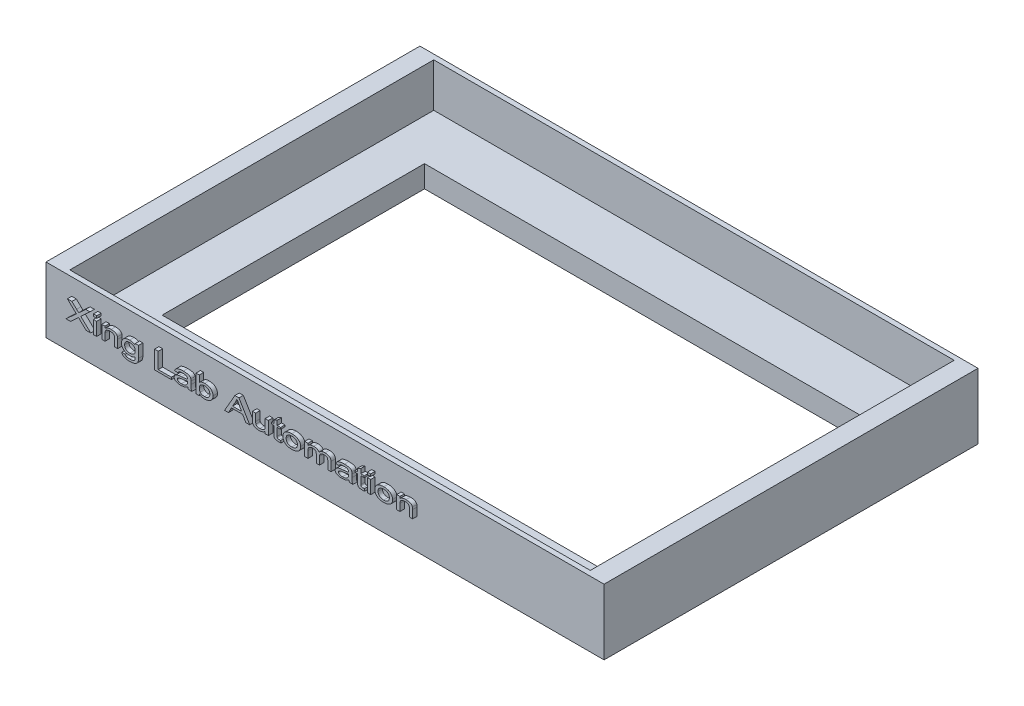
SolidWorks part; units mm, degrees
ref_plane "前视基准面" through (0, 0, 0) normal (0, 0, 1) x (1, 0, 0)
ref_plane "上视基准面" through (0, 0, 0) normal (0, 1, 0) x (1, 0, 0)
ref_plane "右视基准面" through (0, 0, 0) normal (1, 0, 0) x (0, 0, -1)
other "Configuration Table"
sketch "草图1" plane through (0, 0, 0) normal (0, 1, 0) x (1, 0, 0)
  line L0 (-59.5, 42.75) -> (-59.5, -42.7501)
  line L1 (-63.8, -42.75) -> (63.8, -42.75)
  line L3 (-63.8, 42.75) -> (63.8, 42.75)
  line L4 (63.8, -42.75) -> (63.8, 42.75)
  line L5 (-63.8, -42.75) -> (63.8, 42.75) construction
  line L6 (-63.8, 42.75) -> (63.8, -42.75) construction
  line L8 (-63.8, 42.75) -> (-63.8, -42.75)
  line L15 (-59.5, -41.6001) -> (59.5, -41.6001)
  line L17 (-59.5, -42.7501) -> (59.5, -42.7501)
  line L21 (-59.5, 41.6049) -> (59.5, 41.6049)
  line L23 (-50, -30) -> (50, -30)
  line L24 (-50, -30) -> (-50, 30)
  line L25 (-50, 30) -> (50, 30)
  line L26 (50, -30) -> (50, 30)
  line L27 (-50, -30) -> (50, 30) construction
  line L28 (-50, 30) -> (50, -30) construction
  line L30 (1.5, -30) -> (1.5, 30)
  line L32 (-1.5, -30) -> (-1.5, 30)
  line L33 (1.5, -30) -> (-1.5, 30) construction
  line L34 (1.5, 30) -> (-1.5, -30) construction
  line L35 (50, 1.5) -> (-50, 1.5)
  line L37 (50, -1.5) -> (-50, -1.5)
  line L39 (50, 1.5) -> (-50, -1.5) construction
  line L40 (50, -1.5) -> (-50, 1.5) construction
  line L41 (59.5, 42.75) -> (59.5, -42.7501)
  point P0 (0, 0)
  point P18 (0, 0)
  point P23 (0, 0)
  point P28 (0, 0)
  dimension "D1" = 127.6
  dimension "D2" = 85.5
  dimension "D7" = 119
  dimension "D8" = 1.15
  dimension "D9" = 60
  dimension "D10" = 100
  dimension "D11" = 100
extrude "凸台-拉伸2" add sketch "草图1" along normal blind 5 contours L21 L15 L26 L23 L24 L25 region at (0, 0, -40.1529)
extrude "凸台-拉伸3" add sketch "草图1<4>" along normal blind 15 contours L3 L1 | L21 L3 | L3 L1 L4 | L15 L1 region at (0, 0, -42.1774) region at (-61.65, 0, 0) region at (61.65, 0, 0) region at (0, 0, 42.1751)
sketch "草图1<4>" plane through (0, 0, 0) normal (0, 1, 0) x (1, 0, 0) same geometry as "草图1"
sketch "草图2" plane through (0, 0, 42.75) normal (0, 0, 1) x (1, 0, 0)
  text T0 "Xing Lab Automation" font "Helvetica" height in points 16
extrude "凸台-拉伸4" add sketch "草图2" along normal blind 1
